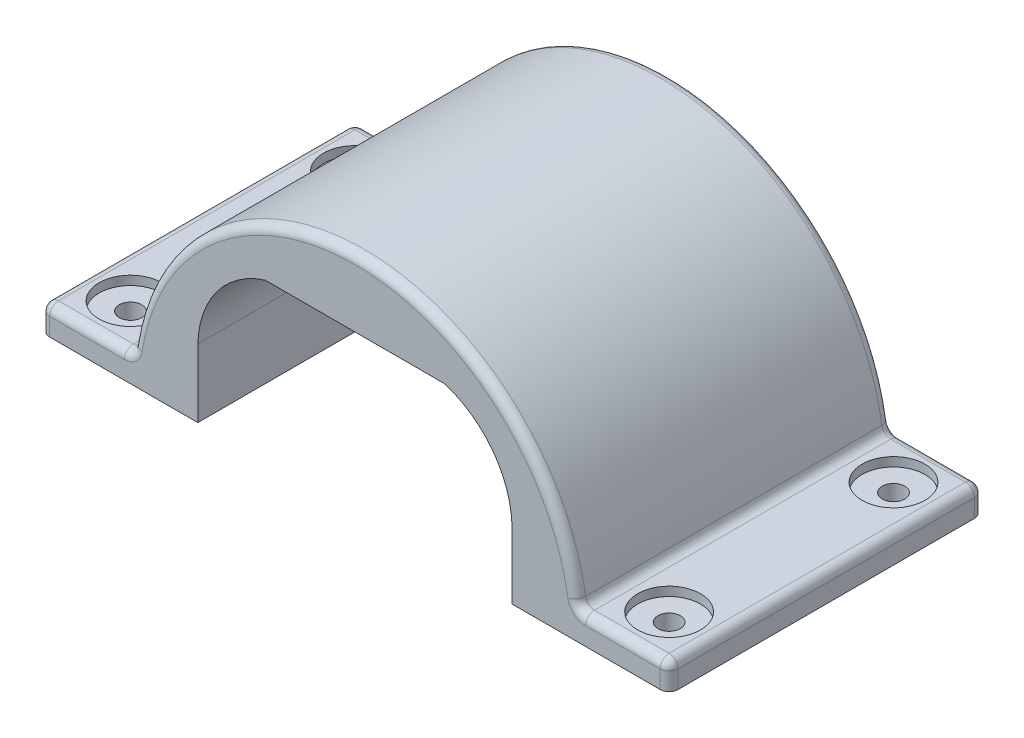
SolidWorks part; units mm, degrees
ref_plane "Alzado" through (0, 0, 0) normal (0, 0, 1) x (1, 0, 0)
ref_plane "Planta" through (0, 0, 0) normal (0, 1, 0) x (1, 0, 0)
ref_plane "Vista lateral" through (0, 0, 0) normal (1, 0, 0) x (0, 0, -1)
sketch "Croquis1" plane through (0, 0, 0) normal (0, 1, 0) x (1, 0, 0)
  line L1 (-33.2801, -13.9599) -> (36.7199, -13.9599)
  line L2 (-33.2801, -13.9599) -> (-33.2801, -48.9599)
  line L3 (-33.2801, -48.9599) -> (36.7199, -48.9599)
  line L4 (36.7199, -13.9599) -> (36.7199, -48.9599)
  dimension "D1" = 35
  dimension "D2" = 70
extrude "Saliente-Extruir1" add sketch "Croquis1" along normal blind 30
sketch "Croquis2" plane through (0, 0, 48.9599) normal (0, 0, 1) x (1, 0, 0)
  line L0 (-33.2801, 0) -> (36.7199, 0) construction
  line L1 (-15.7801, 0) -> (-15.7801, 7.5966)
  line L2 (-8.2801, 17.5) -> (11.7199, 17.5)
  line L3 (19.2199, 0) -> (19.2199, 7.5966)
  arc A0 (-15.7801, 0) -> (19.2199, 0) centre (1.7199, 0) ccw
  arc A1 (19.2199, 7.5966) -> (11.7199, 17.5) centre (8.5341, 7.2957) ccw
  arc A2 (-15.7801, 7.5966) -> (-8.2801, 17.5) centre (-5.0943, 7.2957) cw
  point P9 (1.7199, 17.5)
  dimension "D1" = 35
  dimension "D5" = 10.69
  dimension "D6" = 10.69
  dimension "D2" = 7.5966
  dimension "D3" = 20
  dimension "D4" = 7.5966
extrude "Cortar-Extruir1" cut sketch "Croquis2" against normal blind 310
sketch "Croquis3" plane through (0, 0, 48.9599) normal (0, 0, 1) x (1, 0, 0)
  line L0 (36.7199, 30) -> (36.7199, 0) construction
  line L10 (-33.2801, 30) -> (36.7199, 30)
  line L11 (-33.2801, 30) -> (-33.2801, 3)
  line L13 (36.7199, 30) -> (36.7199, 3)
  line L20 (-33.2801, 3) -> (-23.0995, 3)
  line L21 (26.5392, 3) -> (36.7199, 3)
  arc A2 (26.5392, 3) -> (-23.0995, 3) centre (1.7199, 0) ccw
extrude "Cortar-Extruir2" cut sketch "Croquis3" against normal blind 310
sketch "Croquis4" plane through (0, 3, 0) normal (0, 1, 0) x (1, 0, 0)
  line L0 (-33.2801, -13.9599) -> (-15.7801, -13.9599) construction
  line L1 (-33.2801, -13.9599) -> (-33.2801, -48.9599) construction
  line L2 (-33.2801, -48.9599) -> (-15.7801, -48.9599) construction
  line L3 (35.0392, -48.9599) -> (36.7199, -48.9599) construction
  line L4 (36.7199, -13.9599) -> (36.7199, -48.9599) construction
  line L5 (35.0392, -13.9599) -> (36.7199, -13.9599) construction
  circle A0 centre (-28.2801, -18.9599) radius 3.5
  circle A1 centre (-28.2801, -43.9599) radius 3.5
  circle A2 centre (31.7199, -18.9599) radius 3.5
  circle A3 centre (31.7199, -43.9599) radius 3.5
  dimension "D1" = 7
  dimension "D2" = 7
  dimension "7" = 7
  dimension "D4" = 7
  dimension "D5" = 5
  dimension "D6" = 5
  dimension "D7" = 5
  dimension "D8" = 5
  dimension "D9" = 5
  dimension "D10" = 5
  dimension "D11" = 5
  dimension "D12" = 5
extrude "Cortar-Extruir3" cut sketch "Croquis4" against normal blind 1
ref_plane "Plano1" through (0, 0, 31.4599) normal (0, 0, -1) x (-1, 0, 0)
ref_plane "Plano2" through (1.7199, 0, 0) normal (1, 0, 0) x (0, 0, -1)
fillet "Redondeo1" radius 1 10 edges at (1.7199, 25, 48.9599) (1.7199, 25, 13.9599) (-28.1898, 3, 48.9599) (31.6296, 3, 48.9599) (31.6296, 3, 13.9599) (-28.1898, 3, 13.9599) (-33.2801, 3, 31.4599) (-23.0995, 3, 31.4599) (36.7199, 3, 31.4599) (26.5392, 3, 31.4599)
fillet "Redondeo2" radius 1 8 edges at (36.427, 2.7071, 48.667) (36.427, 2.7071, 14.2527) (-32.9872, 2.7071, 14.2527) (-32.9872, 2.7071, 48.667) (36.7199, 1, 48.9599) (36.7199, 1, 13.9599) (-33.2801, 1, 13.9599) (-33.2801, 1, 48.9599)
sketch "Croquis5" plane through (0, 2, 0) normal (0, 1, 0) x (1, 0, 0)
  circle A0 centre (-28.2801, -18.9599) radius 1.25
  circle A1 centre (31.7199, -18.9599) radius 1.25
  circle A2 centre (31.7199, -43.9599) radius 1.25
  circle A3 centre (-28.2801, -43.9599) radius 1.25
  dimension "D1" = 2.5
  dimension "D2" = 2.5
  dimension "D3" = 2.5
  dimension "D4" = 2.5
extrude "Cortar-Extruir4" cut sketch "Croquis5" against normal blind 10
